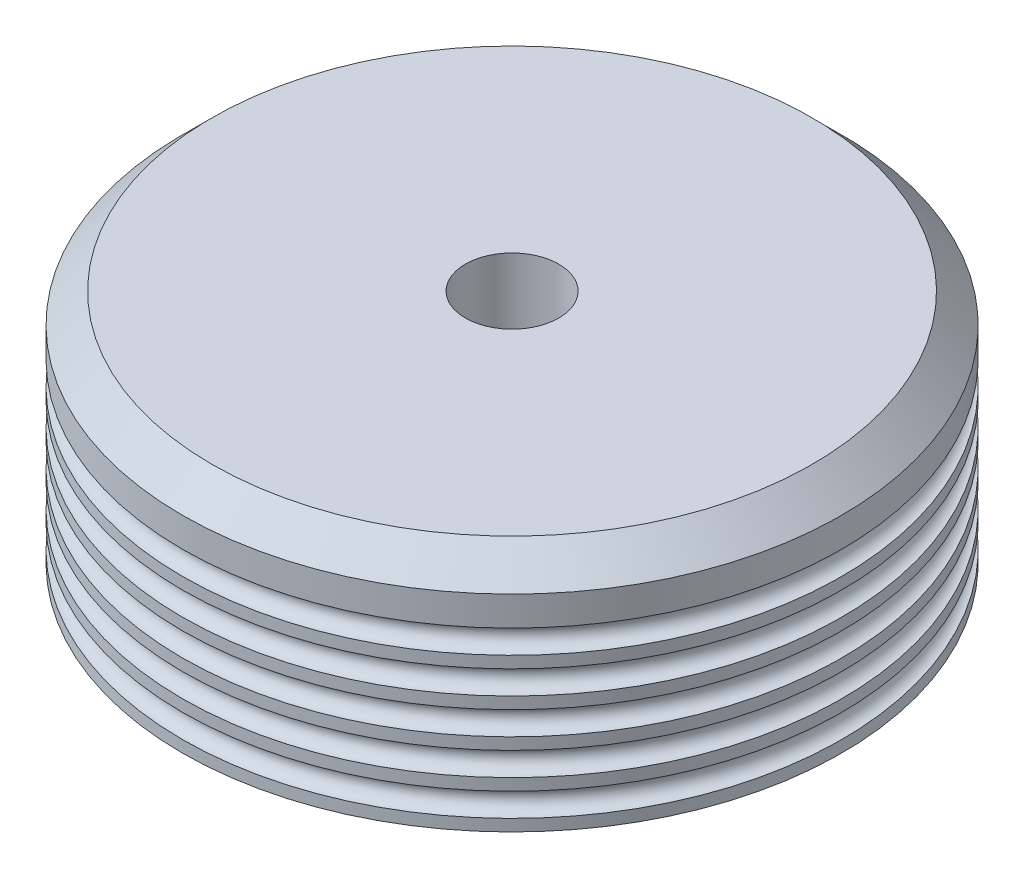
SolidWorks part; units mm, degrees
ref_plane "Front Plane" through (0, 0, 0) normal (0, 0, 1) x (1, 0, 0)
ref_plane "Top Plane" through (0, 0, 0) normal (0, 1, 0) x (1, 0, 0)
ref_plane "Right Plane" through (0, 0, 0) normal (1, 0, 0) x (0, 0, -1)
ref_axis "y" through (0, 66.2934, 0) along (0, -1, 0)
sketch "Sketch1" plane through (0, 0, 0) normal (0, 0, 1) x (1, 0, 0)
  line L0 (-3.9688, 20) -> (-28, 20)
  line L1 (-28, 20) -> (-28, 15)
  line L2 (-3.9688, 20) -> (-3.9688, 0)
  line L3 (-28, 10) -> (-28, 9)
  line L4 (-28, 13) -> (-28, 12)
  line L6 (-28, 7) -> (-28, 6)
  line L7 (-28, 4) -> (-28, 3)
  line L8 (-28, 1) -> (-28, 0)
  line L9 (0, 66.2934) -> (0, -3.1568) construction
  line L10 (-28, 0) -> (-3.9688, 0)
  arc A0 (-28, 15) -> (-28, 13) centre (-28, 14) cw
  arc A1 (-28, 12) -> (-28, 10) centre (-28, 11) cw
  arc A2 (-28, 9) -> (-28, 7) centre (-28, 8) cw
  arc A3 (-28, 6) -> (-28, 4) centre (-28, 5) cw
  arc A4 (-28, 3) -> (-28, 1) centre (-28, 2) cw
  point P13 (0, 0)
  dimension "D1" = 1
  dimension "D3" = 3
  dimension "D4" = 3.9688
  dimension "D5" = 28
  dimension "D6" = 20
  dimension "D2" = 5
revolve "body" add sketch "Sketch1" angle 360 about axis through (0, 66.2934, 0) along (0, -1, 0)
chamfer "Chamfer1" distance 2.5 angle 45 1 edges at (0, 20, 28)
sketch "Sketch2" plane through (0, 0, 0) normal (0, -1, 0) x (1, 0, 0)
  line L0 (-5.071, 8.7832) -> (-10.1735, 17.621)
  line L1 (5.071, 8.7832) -> (10.1735, 17.621)
  line L3 (-0.3768, 0.6526) -> (-25000.3768, 43301.9227) construction
  line L4 (-1.6513, -2.8601) -> (24998.3487, 43298.4101) construction
  line L5 (0, 0) -> (0, 50000) construction
  arc A0 (-3.5006, 8.2574) -> (3.5006, 8.2574) centre (0, 0) cw
  circle A1 centre (0, 0) radius 3.9688 construction
  arc A2 (-3.5006, 8.2574) -> (-5.071, 8.7832) centre (-3.9885, 9.4082) cw
  arc A3 (3.5006, 8.2574) -> (5.071, 8.7832) centre (3.9885, 9.4082) ccw
  arc A4 (-10.1735, 17.621) -> (-8.9851, 21.1724) centre (-8.0084, 18.871) cw
  arc A5 (10.1735, 17.621) -> (8.9851, 21.1724) centre (8.0084, 18.871) ccw
  arc A6 (-8.9851, 21.1724) -> (8.9851, 21.1724) centre (0, 0) cw
  circle A8 centre (0, 0) radius 28 construction
  point P21 (-8.5739, 23.362)
  point P23 (7.8688, 24.5524)
  dimension "D1" = 5
  dimension "D4" = 1.25
  dimension "D5" = 5
  dimension "D6" = 2.5
  dimension "D2" = 30
  dimension "D3" = 30
extrude "pocket" cut sketch "Sketch2" against normal offset from surface (12.5 mm away) 7.5 up to face at (0, 20, 25.5)
pattern_circular "CirPattern1" count 4 every 90 about axis through (0, 66.2934, 0) along (0, -1, 0) of "pocket"
fillet "Fillet1" radius 2.5 64 edges at (-4.3854, 0, -8.2229) (0, 0, -8.9688) (4.3854, 0, -8.2229) (7.6222, 0, -13.2021) (10.3792, 0, -19.6644) (0, 0, -23) (-10.3792, 0, -19.6644) (19.6644, 0, 10.3792) (23, 0, 0) (19.6644, 0, -10.3792) (13.2021, 0, -7.6222) (8.2229, 0, -4.3854) (8.9688, 0, 0) (8.2229, 0, 4.3854) (-10.3792, 0, 19.6644) (0, 0, 23) (10.3792, 0, 19.6644) (7.6222, 0, 13.2021) (4.3854, 0, 8.2229) (0, 0, 8.9688) (-4.3854, 0, 8.2229) (-8.2229, 0, 4.3854) (-8.9688, 0, 0) (-8.2229, 0, -4.3854) (-13.2021, 0, -7.6222) (-19.6644, 0, -10.3792) (-23, 0, 0) (-19.6644, 0, 10.3792) (7.6222, 12.5, -13.2021) (10.3792, 12.5, -19.6644) (0, 12.5, -23) (-10.3792, 12.5, -19.6644) (-7.6222, 12.5, -13.2021) (-4.3854, 12.5, -8.2229) (0, 12.5, -8.9688) (4.3854, 12.5, -8.2229) (13.2021, 12.5, 7.6222) (19.6644, 12.5, 10.3792) (23, 12.5, 0) (19.6644, 12.5, -10.3792) (13.2021, 12.5, -7.6222) (8.2229, 12.5, -4.3854) (8.9688, 12.5, 0) (8.2229, 12.5, 4.3854) (-7.6222, 12.5, 13.2021) (-10.3792, 12.5, 19.6644) (0, 12.5, 23) (10.3792, 12.5, 19.6644) (7.6222, 12.5, 13.2021) (4.3854, 12.5, 8.2229) (0, 12.5, 8.9688) (-4.3854, 12.5, 8.2229) (-13.2021, 12.5, -7.6222) (-19.6644, 12.5, -10.3792) (-23, 12.5, 0) (-19.6644, 12.5, 10.3792) (-13.2021, 12.5, 7.6222) (-8.2229, 12.5, 4.3854) (-8.9688, 12.5, 0) (-8.2229, 12.5, -4.3854) (-7.6222, 0, -13.2021) (13.2021, 0, 7.6222) (-7.6222, 0, 13.2021) (-13.2021, 0, 7.6222)
equation "\"ridge_spacing\"= 3mm"
equation "\"scallop_depth\" = 1mm"
equation "\"D1@Sketch1\"=\"scallop_depth\""
equation "\"num_scallops\"= 5"
equation "\"D2@Sketch1\"=\"num_scallops\""
equation "\"D3@Sketch1\"=\"ridge_spacing\""
equation "\"tube_id\"= 56mm"
equation "\"D5@Sketch1\"=\"tube_id\"/2"
